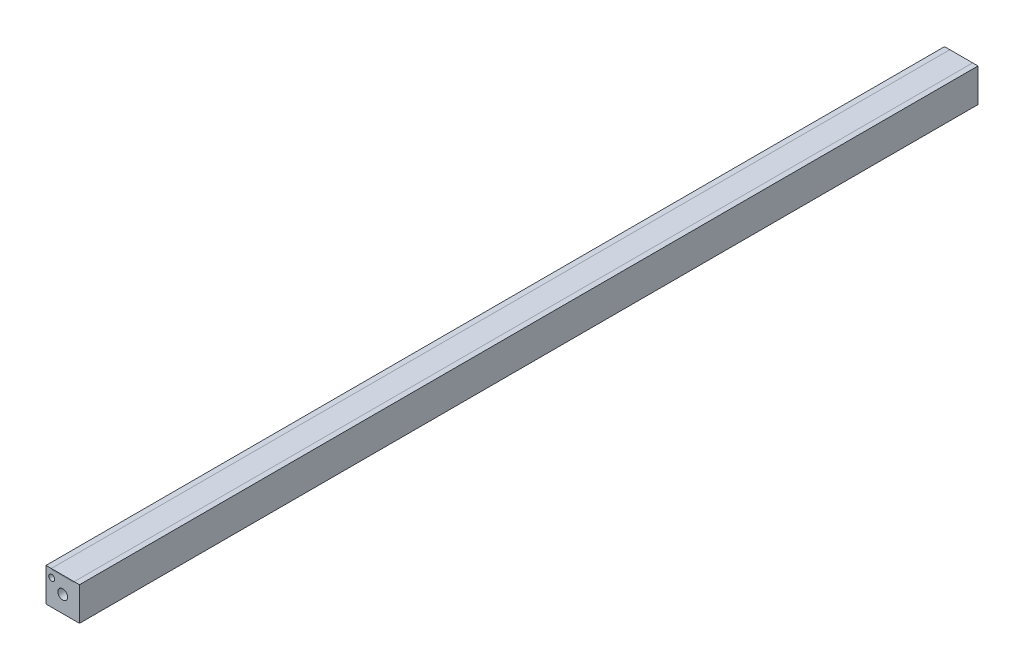
SolidWorks part; units mm, degrees
material "1060 Alloy"
ref_plane "Front Plane" through (0, 0, 0) normal (0, 0, 1) x (1, 0, 0)
ref_plane "Top Plane" through (0, 0, 0) normal (0, 1, 0) x (1, 0, 0)
ref_plane "Right Plane" through (0, 0, 0) normal (1, 0, 0) x (0, 0, -1)
sketch "Sketch1" plane through (0, 0, 0) normal (0, 0, 1) x (1, 0, 0)
  line L1 (0, 0) -> (18.63, 0)
  line L2 (0, 0) -> (0, -18.63)
  line L3 (0, -18.63) -> (18.63, -18.63)
  line L4 (18.63, 0) -> (18.63, -18.63)
  dimension "D1" = 18.63
extrude "Boss-Extrude1" add sketch "Sketch1" along normal blind 500
sketch "Sketch2" plane through (0, 0, 0) normal (0, 0, -1) x (-1, 0, 0)
  line L0 (-9.315, 0) -> (-9.315, -18.63) construction
  line L1 (-18.63, 0) -> (0, 0) construction
  line L2 (0, -18.63) -> (-18.63, -18.63) construction
  line L3 (-18.63, -9.315) -> (0, -9.315) construction
  line L4 (-18.63, -18.63) -> (-18.63, 0) construction
  line L5 (0, 0) -> (0, -18.63) construction
  circle A0 centre (-9.315, -9.315) radius 2.71
  dimension "D1" = 5.42
extrude "Cut-Extrude1" cut sketch "Sketch2" against normal blind 24
sketch "Sketch3" plane through (0, 0, 500) normal (0, 0, 1) x (1, 0, 0)
  circle A1 centre (9.315, -9.315) radius 2.71
  circle A2 centre (9.315, -9.315) radius 2.71
  dimension "D1" = 0
extrude "Cut-Extrude2" cut sketch "Sketch3" against normal blind 24
sketch "Sketch4" plane through (0, 0, 0) normal (0, 0, -1) x (-1, 0, 0)
  circle A0 centre (-14.95, -3.73) radius 1.67
  circle A1 centre (-14.95, -3.73) radius 1.585 construction
  dimension "D1" = 3.34
extrude "Cut-Extrude3" cut sketch "Sketch4" against normal blind 10
sketch "Sketch5" plane through (0, 0, 500) normal (0, 0, 1) x (1, 0, 0)
  circle A0 centre (3.18, -4.345) radius 1.67
  circle A1 centre (3.18, -4.345) radius 1.25 construction
  dimension "D1" = 3.34
extrude "Cut-Extrude4" cut sketch "Sketch5" against normal blind 10
sketch "Sketch6" plane through (0, 0, 0) normal (0, 1, 0) x (-1, 0, 0)
  line L1 (-15.665, 0) -> (-2.965, 0)
  line L2 (-15.665, 0) -> (-15.665, 500)
  line L3 (-15.665, 500) -> (-2.965, 500)
  line L4 (-2.965, 0) -> (-2.965, 500)
  line L5 (-18.63, 0) -> (0, 0) construction
  line L6 (-18.63, 500) -> (0, 500) construction
  line L7 (-9.315, 0) -> (-9.315, 500) construction
  line L9 (0, 500) -> (0, 0) construction
  line L10 (-18.63, 500) -> (-18.63, 0) construction
  dimension "D1" = 12.7
extrude "Cut-Extrude5" cut sketch "Sketch6" against normal blind 0.5
sketch "Sketch7" plane through (0, 0, 0) normal (0, 1, 0) x (-1, 0, 0)
  line L0 (-9.315, 500) -> (-9.315, 0) construction
  line L1 (-15.665, 0) -> (-2.965, 0)
  line L2 (-15.665, 0) -> (-15.665, 500)
  line L3 (-15.665, 500) -> (-2.965, 500)
  line L4 (-2.965, 0) -> (-2.965, 500)
  line L8 (-18.63, 0) -> (-15.665, 0) construction
  line L9 (-18.63, 500) -> (-15.665, 500) construction
  line L10 (-15.665, 500) -> (-15.665, 0) construction
  line L12 (-2.965, 0) -> (-2.965, 500) construction
  dimension "D1" = 12.7
extrude "Boss-Extrude2" add sketch "Sketch7" against normal up to surface (0.5 mm away) separate body up to face at (9.315, -0.5, 250)
